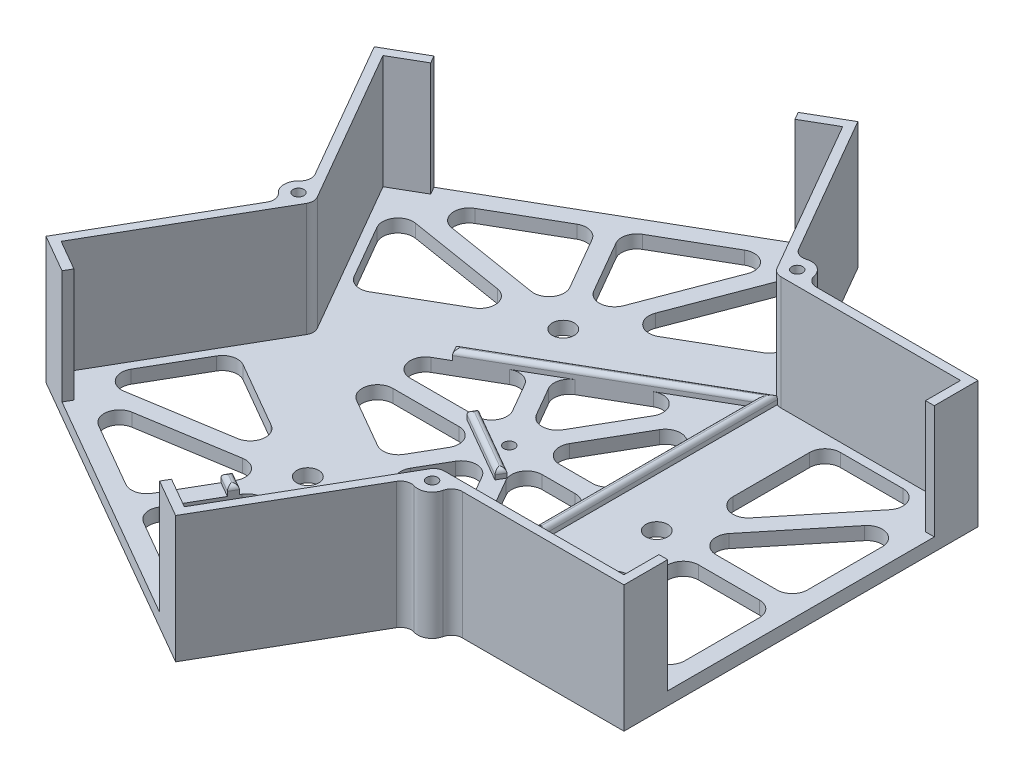
SolidWorks part; units mm, degrees
ref_plane "Front Plane" through (0, 0, 0) normal (0, 0, 1) x (1, 0, 0)
ref_plane "Top Plane" through (0, 0, 0) normal (0, 1, 0) x (1, 0, 0)
ref_plane "Right Plane" through (0, 0, 0) normal (1, 0, 0) x (0, 0, -1)
sketch "Sketch1" plane through (0, 0, 0) normal (0, 1, 0) x (1, 0, 0)
  line L0 (-19.4617, -68.9294) -> (-33.415, -32.2478)
  line L1 (-15.5479, 2.6989) -> (-16.7979, 0.5338)
  line L2 (50.5658, -38.8837) -> (50.5658, 42.1163)
  line L3 (-49.5423, -56.1811) -> (-14.4683, -76.4311)
  line L4 (-66.1729, -6.1649) -> (-66.1729, -0.3837)
  line L5 (-49.5423, -56.1811) -> (-84.6163, -35.9311)
  line L6 (-84.6163, -35.9311) -> (-68.1729, -7.4503)
  line L7 (-84.6163, 39.1637) -> (-68.1729, 10.683)
  line L8 (-14.4683, 79.6637) -> (1.9751, 51.183)
  line L9 (-66.1729, 1.6163) -> (-18.4823, 1.6163)
  line L10 (-84.6163, 39.1637) -> (-14.4683, 79.6637)
  line L11 (50.5658, 42.1163) -> (17.679, 42.1163)
  line L12 (50.5658, -38.8837) -> (17.679, -38.8837)
  line L13 (-14.4683, -76.4311) -> (1.9751, -47.9503)
  line L14 (2.0883, 48.8082) -> (7.095, 45.9176)
  line L15 (-33.7744, -24.8702) -> (-66.1729, -6.1649)
  line L16 (8.8271, 44.9176) -> (-15.0182, 3.6163)
  line L17 (-68.1729, -7.4503) -> (-68.1729, 10.683)
  line L18 (-38.91, -26.5239) -> (-65.6522, -11.0843)
  line L19 (19.5658, -4.0044) -> (19.5658, -34.8837)
  line L20 (1.9751, -47.9503) -> (17.679, -38.8837)
  line L21 (1.9751, 51.183) -> (17.679, 42.1163)
  line L22 (15.5658, -0.3837) -> (15.5658, -37.7943)
  line L23 (-29.1746, 35.3773) -> (-2.4324, 50.817)
  line L24 (10.5591, 43.9176) -> (15.5658, 41.027)
  line L25 (15.5658, -37.7943) -> (10.5591, -40.6849)
  line L26 (-30.3103, 30.1029) -> (2.0883, 48.8082)
  line L27 (8.8271, -41.6849) -> (-15.0182, -0.3837)
  line L28 (-17.3276, 3.6163) -> (-31.7524, 28.6007)
  line L29 (-17.4229, 1.6163) -> (-14.9229, 1.6163)
  line L30 (-17.3276, -0.3837) -> (-31.7524, -25.368)
  line L31 (-15.5479, 0.5338) -> (-16.7979, 2.6989)
  line L32 (-65.6522, 14.317) -> (-38.91, 29.7566)
  line L33 (19.5658, 38.1163) -> (19.5658, 7.2371)
  line L34 (-2.4324, -47.5843) -> (-29.1746, -32.1447)
  line L35 (-66.1729, 9.3975) -> (-33.7744, 28.1029)
  line L36 (15.5658, 41.027) -> (15.5658, 3.6163)
  line L37 (2.0883, -45.5755) -> (-30.3103, -26.8702)
  line L38 (7.095, 45.9176) -> (-16.1729, 5.6163)
  line L39 (-66.1729, -0.3837) -> (-19.637, -0.3837)
  line L40 (10.5591, -40.6849) -> (-12.7088, -0.3837)
  line L41 (10.5591, 43.9176) -> (-12.7088, 3.6163)
  line L42 (-66.1729, 3.6163) -> (-19.637, 3.6163)
  line L43 (7.095, -42.6849) -> (-16.1729, -2.3837)
  line L44 (-13.8635, 1.6163) -> (14.9859, 1.6163)
  line L45 (-16.1729, 5.6163) -> (-30.3103, 30.1029)
  line L46 (-12.7088, 3.6163) -> (15.5658, 3.6163)
  line L47 (-19.637, -0.3837) -> (-33.7744, -24.8702)
  line L48 (-19.637, 3.6163) -> (-33.7744, 28.1029)
  line L49 (-12.7088, -0.3837) -> (15.5658, -0.3837)
  line L50 (-16.1729, -2.3837) -> (-30.3103, -26.8702)
  line L51 (-53.8858, -0.3837) -> (-28.1992, -15.2138)
  line L52 (4.4155, -30.0439) -> (4.4155, -0.3837)
  line L53 (0.9514, 35.2766) -> (-24.7351, 20.4465)
  line L54 (4.4155, 3.6163) -> (4.4155, 33.2766)
  line L55 (-78.2327, 36.1069) -> (-65.6522, 14.317)
  line L56 (-75.6229, 39.7373) -> (-49.2744, 54.9496)
  line L57 (-15.0128, 72.6069) -> (-2.4324, 50.817)
  line L58 (-15.0128, -69.3743) -> (-2.4324, -47.5843)
  line L59 (-45.8103, -53.717) -> (-19.4617, -68.9294)
  line L60 (-49.2744, -51.717) -> (-75.6229, -36.5046)
  line L61 (-78.2327, -32.8743) -> (-65.6522, -11.0843)
  line L62 (44.7266, 38.1163) -> (19.5658, 38.1163)
  line L63 (-28.1992, 18.4465) -> (-53.8858, 3.6163)
  line L64 (46.5658, -30.8084) -> (46.5658, -0.3837)
  line L65 (44.7266, -34.8837) -> (19.5658, -34.8837)
  line L66 (-24.7351, -17.2138) -> (0.9514, -32.0439)
  line L67 (-38.91, -26.5239) -> (-78.2327, -32.8743)
  line L68 (-15.0128, -69.3743) -> (-29.1746, -32.1447)
  line L69 (-66.1729, 3.6163) -> (-66.1729, 9.3975)
  line L70 (44.7266, 38.1163) -> (19.5658, 7.2371)
  line L71 (7.095, -42.6849) -> (2.0883, -45.5755)
  line L72 (-29.1746, 35.3773) -> (-15.0128, 72.6069)
  line L73 (-78.2327, 36.1069) -> (-38.91, 29.7566)
  line L74 (-36.8791, -30.2478) -> (-75.6229, -36.5046)
  line L75 (46.5658, 34.041) -> (21.7753, 3.6163)
  line L76 (21.7753, -0.3837) -> (46.5658, -30.8084)
  line L77 (-33.415, 35.4804) -> (-19.4617, 72.162)
  line L78 (-75.6229, 39.7373) -> (-36.8791, 33.4804)
  line L79 (46.5658, 3.6163) -> (46.5658, 34.041)
  line L80 (19.5658, -4.0044) -> (44.7266, -34.8837)
  line L81 (-45.8103, 56.9496) -> (-19.4617, 72.162)
  line L82 (46.5658, 3.6163) -> (21.7753, 3.6163)
  line L83 (-33.415, 35.4804) -> (-45.8103, 56.9496)
  line L84 (-45.8103, -53.717) -> (-33.415, -32.2478)
  line L85 (46.5658, -0.3837) -> (21.7753, -0.3837)
  line L86 (-36.8791, 33.4804) -> (-49.2744, 54.9496)
  line L87 (-49.2744, -51.717) -> (-36.8791, -30.2478)
  circle A0 centre (-33.0423, -27.6023) radius 2.5
  circle A1 centre (-33.0423, 30.8349) radius 2.5
  circle A2 centre (17.5658, 1.6163) radius 2.5
  circle A3 centre (-16.1729, 1.6163) radius 1.25
  point P6 (50.5658, 1.6163)
  point P11 (-49.5423, -56.1811)
  point P14 (-49.5423, 59.4137)
  point P15 (-49.5423, -56.1811)
  point P26 (-68.1729, 1.6163)
  point P32 (9.8271, -43.417)
  point P36 (9.8271, 46.6496)
  point P64 (-16.1729, 1.6163)
  point P94 (-16.1729, 1.6163)
extrude "Boss-Extrude1" add sketch "Sketch1" along normal blind 3 contours L21 L8 L10 L7 L17 L6 L5 L3 L13 L20 L12 L2 L11 A3 A2 A1 A0 L87 L60 L74 L86 L78 | L69 L42 L63 L48 L35 | L53 L38 L14 L26 L45 | L54 L46 L36 L24 L41 | L52 L40 L25 L22 L49 | L71 L43 L66 L50 L37 | L51 L39 L4 L15 L47 region at (34.1224, 0, 36.8187) region at (-47.1024, 0, 10.9831) region at (-11.6196, 0, -34.7018) region at (10.2032, 0, 18.8697) region at (10.2032, 0, -22.1024) region at (-47.1024, 0, -14.2157) region at (-11.6196, 0, 31.4691)
sketch "Sketch2" plane through (0, 3, 0) normal (0, 1, 0) x (1, 0, 0)
  line L1 (-14.4683, 79.6637) -> (1.9751, 51.183)
  line L2 (1.9751, 51.183) -> (17.679, 42.1163)
  line L3 (17.679, 42.1163) -> (50.5658, 42.1163)
  line L5 (50.5658, -38.8837) -> (17.679, -38.8837)
  line L6 (17.679, -38.8837) -> (1.9751, -47.9503)
  line L7 (1.9751, -47.9503) -> (-14.4683, -76.4311)
  line L9 (-84.6163, -35.9311) -> (-68.1729, -7.4503)
  line L10 (-68.1729, -7.4503) -> (-68.1729, 10.683)
  line L11 (-68.1729, 10.683) -> (-84.6163, 39.1637)
  line L12 (-60.6289, 1.6163) -> (-62.9383, 1.6163)
  line L13 (6.055, 40.1163) -> (7.2097, 42.1163)
  line L14 (9.8271, -43.417) -> (7.316, -39.0678)
  line L15 (-60.6289, 1.6163) -> (-81.8843, 38.4317)
  line L17 (-15.2003, 76.9317) -> (6.055, 40.1163)
  line L18 (6.055, 40.1163) -> (48.5658, 40.1163)
  line L20 (48.5658, -36.8837) -> (6.055, -36.8837)
  line L21 (6.055, -36.8837) -> (-15.2003, -73.699)
  line L23 (-81.8843, -35.199) -> (-60.6289, 1.6163)
  line L24 (-15.2003, -73.699) -> (-81.8843, -35.199) construction
  line L25 (-14.4683, -76.4311) -> (-84.6163, -35.9311) construction
  line L26 (-81.8843, -35.199) -> (-74.9561, -39.199)
  line L27 (-74.9561, -39.199) -> (-75.9561, -40.9311)
  line L28 (-14.4683, -76.4311) -> (-84.6163, -35.9311) construction
  line L29 (-75.9561, -40.9311) -> (-84.6163, -35.9311)
  line L30 (-15.2003, -73.699) -> (-22.1285, -69.699)
  line L31 (-22.1285, -69.699) -> (-23.1285, -71.4311)
  line L32 (-23.1285, -71.4311) -> (-14.4683, -76.4311)
  line L33 (48.5658, 40.1163) -> (48.5658, 32.1163)
  line L34 (48.5658, 40.1163) -> (48.5658, -36.8837) construction
  line L35 (50.5658, 42.1163) -> (50.5658, -38.8837) construction
  line L36 (-84.6163, 39.1637) -> (-14.4683, 79.6637) construction
  line L37 (-81.8843, 38.4317) -> (-15.2003, 76.9317) construction
  line L38 (48.5658, 32.1163) -> (50.5658, 32.1163)
  line L39 (50.5658, -38.8837) -> (50.5658, 42.1163) construction
  line L40 (50.5658, 32.1163) -> (50.5658, 42.1163)
  line L41 (48.5658, -36.8837) -> (48.5658, -28.8837)
  line L42 (48.5658, -28.8837) -> (50.5658, -28.8837)
  line L43 (50.5658, -28.8837) -> (50.5658, -38.8837)
  line L44 (-15.2003, 76.9317) -> (-22.1285, 72.9317)
  line L45 (-22.1285, 72.9317) -> (-23.1285, 74.6637)
  line L46 (-84.6163, 39.1637) -> (-14.4683, 79.6637) construction
  line L47 (-23.1285, 74.6637) -> (-14.4683, 79.6637)
  line L48 (-81.8843, 38.4317) -> (-74.9561, 42.4317)
  line L49 (-74.9561, 42.4317) -> (-75.9561, 44.1637)
  line L50 (-75.9561, 44.1637) -> (-84.6163, 39.1637)
  line L51 (-84.6163, -35.9311) -> (-62.9383, 1.6163) construction
  line L52 (-63.1509, 1.6163) -> (-68.1729, 1.6163)
  line L53 (-62.9383, 1.6163) -> (-84.6163, 39.1637) construction
  line L54 (7.2097, -38.8837) -> (-14.4683, -76.4311) construction
  line L55 (7.2097, -38.8837) -> (6.055, -36.8837)
  line L56 (50.5658, -38.8837) -> (7.2097, -38.8837) construction
  line L57 (7.2097, 42.1163) -> (50.5658, 42.1163) construction
  line L58 (7.316, 42.3005) -> (9.8271, 46.6496)
  line L59 (-14.4683, 79.6637) -> (7.2097, 42.1163) construction
  circle A3 centre (-64.4009, 1.6163) radius 1.25
  circle A4 centre (7.941, -40.1503) radius 1.25
  circle A5 centre (7.941, 43.383) radius 1.25
  dimension "D1" = 2
extrude "Boss-Extrude2" add sketch "Sketch2" along normal blind 26 contours L49 L50 L11 L9 L29 L27 L26 L23 L15 L48 | A3 L10 L9 | A3 L11 L10 | L47 L45 L44 L17 L18 L33 L38 L40 L3 L1 | A5 L3 L2 | A5 L2 L1 | L43 L42 L41 L20 L21 L30 L31 L32 L7 L5 | A4 L7 L6 | A4 L6 L5 region at (-7.0061, 3, -64.9848) region at (34.1224, 3, 38.0067) region at (-75.629, 3, 22.1328)
sketch "Sketch3" plane through (0, 29, 0) normal (0, 1, 0) x (1, 0, 0)
  line L0 (-84.6163, 39.1637) -> (-64.8095, 4.8573)
  line L1 (-84.6163, -35.9311) -> (-64.8095, -1.6247)
  line L2 (-14.4683, -76.4311) -> (5.3385, -42.1247)
  line L3 (50.5658, -38.8837) -> (10.9521, -38.8837)
  line L4 (50.5658, 42.1163) -> (10.9521, 42.1163)
  line L6 (-14.4683, 79.6637) -> (5.3385, 45.3573)
  line L7 (1.9751, 51.183) -> (17.679, 42.1163)
  line L8 (-68.1729, -7.4503) -> (-68.1729, 10.683)
  line L9 (17.679, -38.8837) -> (1.9751, -47.9503)
  circle A0 centre (-64.4009, 1.6163) radius 3.2667
  circle A1 centre (7.941, 43.383) radius 3.2667
  circle A2 centre (7.941, -40.1503) radius 3.2667
  line M4 (-68.1729, 10.683) -> (-68.1729, -7.4503)
extrude "Cut-Extrude1" cut sketch "Sketch3" against normal through all contours A0 L0 L1 M4 | A2 L2 L9 L3 | A1 L4 L7 L6 region at (-66.6509, 29, -7.6779) region at (3.8139, 29, 45.1282) region at (14.3156, 29, -42.2977)
fillet "Fillet1" radius 2.5 9 edges at (6.055, 16, 36.8837) (-60.6289, 16, -1.6163) (6.055, 16, -40.1163) (5.3385, 14.5, -45.3573) (10.9521, 14.5, -42.1163) (5.3385, 14.5, 42.1247) (10.9521, 14.5, 38.8837) (-64.8095, 14.5, 1.6247) (-64.8095, 14.5, -4.8573)
fillet "Fillet2" radius 3.5 54 edges at (-33.415, 1.5, -35.4804) (-2.4324, 1.5, -50.817) (-19.4617, 1.5, -72.162) (-15.0128, 1.5, -72.6069) (-29.1746, 1.5, -35.3773) (-75.6229, 1.5, -39.7373) (-78.2327, 1.5, -36.1069) (-65.6522, 1.5, -14.317) (-38.91, 1.5, -29.7566) (-36.8791, 1.5, -33.4804) (-49.2744, 1.5, -54.9496) (-45.8103, 1.5, -56.9496) (46.5658, 1.5, -34.041) (44.7266, 1.5, -38.1163) (19.5658, 1.5, -38.1163) (46.5658, 1.5, 30.8084) (44.7266, 1.5, 34.8837) (19.5658, 1.5, 34.8837) (46.5658, 1.5, 0.3837) (46.5658, 1.5, -3.6163) (19.5658, 1.5, -7.2371) (21.7753, 1.5, -3.6163) (19.5658, 1.5, 4.0044) (21.7753, 1.5, 0.3837) (0.9514, 1.5, 32.0439) (4.4155, 1.5, 30.0439) (4.4155, 1.5, 0.3837) (4.4155, 1.5, -3.6163) (4.4155, 1.5, -33.2766) (0.9514, 1.5, -35.2766) (-24.7351, 1.5, -20.4465) (-12.7088, 1.5, 0.3837) (-16.1729, 1.5, 2.3837) (-16.1729, 1.5, -5.6163) (-12.7088, 1.5, -3.6163) (-28.1992, 1.5, -18.4465) (-19.637, 1.5, -3.6163) (-19.637, 1.5, 0.3837) (-28.1992, 1.5, 15.2138) (-24.7351, 1.5, 17.2138) (-53.8858, 1.5, -3.6163) (-53.8858, 1.5, 0.3837) (-2.4324, 1.5, 47.5843) (-19.4617, 1.5, 68.9294) (-15.0128, 1.5, 69.3743) (-29.1746, 1.5, 32.1447) (-33.415, 1.5, 32.2478) (-36.8791, 1.5, 30.2478) (-38.91, 1.5, 26.5239) (-45.8103, 1.5, 53.717) (-49.2744, 1.5, 51.717) (-65.6522, 1.5, 11.0843) (-75.6229, 1.5, 36.5046) (-78.2327, 1.5, 32.8743)
sketch "Sketch4" plane through (0, 3, 0) normal (0, 1, 0) x (1, 0, 0)
  line L0 (-57.3499, 1.6163) -> (-43.5001, 9.6125)
  line L1 (-61.3499, 1.6163) -> (-45.5001, 10.7672)
  line L2 (4.4155, -34.0439) -> (4.4155, -18.0516)
  line L3 (-57.3499, 1.6163) -> (4.4155, -34.0439)
  line L4 (6.4155, -37.508) -> (6.4155, -19.2063)
  line L5 (-61.3499, 1.6163) -> (6.4155, -37.508)
  line L6 (-65.3499, 1.6163) -> (8.4155, 44.2048)
  line L7 (8.4155, -40.9721) -> (8.4155, 44.2048)
  line L8 (-65.3499, 1.6163) -> (8.4155, -40.9721)
  line L9 (-81.8843, -35.199) -> (-51.8843, 16.7625) construction
  line L10 (-15.2003, -73.699) -> (14.7997, -21.7375) construction
  line L11 (-43.5001, 11.9219) -> (6.4155, -16.8969)
  line L12 (-47.5001, 11.9219) -> (-26.1384, -0.4113)
  line L13 (4.4155, -13.4328) -> (4.4155, 37.2766)
  line L14 (6.4155, -16.8969) -> (6.4155, 40.7407)
  line L15 (-51.8843, 16.7625) -> (14.7997, -21.7375) construction
  line L16 (-52.8843, 15.0304) -> (13.7997, -23.4696) construction
  line L17 (-39.5001, 11.9219) -> (4.4155, -13.4328)
  line L18 (-39.5001, 11.9219) -> (4.4155, 37.2766)
  line L19 (-57.3499, 1.6163) -> (4.4155, 37.2766) construction
  line L20 (-43.5001, 11.9219) -> (6.4155, 40.7407)
  line L21 (-61.3499, 1.6163) -> (6.4155, 40.7407) construction
  line L22 (4.4155, -34.0439) -> (4.4155, 37.2766) construction
  line L23 (-33.1145, 3.6163) -> (-25.1145, 3.6163)
  line L24 (6.4155, -37.508) -> (6.4155, 40.7407) construction
  line L25 (-125.5001, 11.9219) -> (47.4155, -87.911)
  line L28 (-125.5001, 11.9219) -> (47.4155, 111.7548) construction
  line L29 (47.4155, -87.911) -> (47.4155, 111.7548) construction
  line L30 (-22.4725, -2.5278) -> (-16.6121, -5.9113)
  line L31 (-5.9701, -12.0555) -> (-9.9701, -5.1273)
  line L32 (-12.9462, -8.0278) -> (8.4155, -20.361)
  line L33 (-9.9701, -5.1273) -> (-10.9701, -6.8593)
  line L34 (-25.1145, 3.6163) -> (-26.1145, 1.8843)
  line L35 (-39.5001, 11.9219) -> (-40.5001, 13.6539)
  line L36 (4.4155, -13.4328) -> (6.4155, -13.4328)
  line L37 (-126.5001, 10.1898) -> (46.4155, -89.6431)
  line L38 (-47.5244, -48.6859) -> (-40.5624, -36.6275)
  line L39 (-37.0983, -38.6275) -> (-44.0603, -50.6859)
  line L40 (-22.4725, -2.5278) -> (-21.4725, -0.7958)
  line L41 (-16.6121, -5.9113) -> (-15.6121, -4.1793)
  line L42 (4.4155, 37.2766) -> (7.941, 43.383) construction
  circle A0 centre (-63.5157, 1.6163) radius 2.5
  circle A1 centre (7.4984, 42.6163) radius 2.5
  circle A2 centre (7.4984, -39.3837) radius 2.5
  circle A3 centre (-25.6992, -3.8837) radius 3.5
  circle A4 centre (-16.1729, -9.3837) radius 3.5
  dimension "D1" = 2
  dimension "D3" = 2
  dimension "D2" = 2
  dimension "D4" = 41
  dimension "D5" = 2
extrude "Boss-Extrude3" add sketch "Sketch4" along normal blind 2 contours A1 L20 L35 L18 L13 L36 L14 | L39 L25 L38 L37 | L17 L34 L11 L33 region at (-18.0423, 3, 1.6215) region at (5.8908, 3, -39.8319) region at (-39.5423, 3, 38.8606)
fillet "Fillet3" radius 1 14 edges at (-17.2058, 5, -27.1029) (-17.5423, 5, -24.5992) (6.4155, 5, -13.4651) (4.4155, 5, -11.9219) (-17.5423, 5, 0.7555) (-18.5423, 5, 2.4875) (-39.0423, 5, 37.9946) (-40.0423, 5, 39.7266) (-41.2744, 5, 37.8606) (-37.8103, 5, 39.8606) (-10.4701, 5, 5.9933) (-25.6145, 5, -2.7503) (-40.0001, 5, -12.7879) (5.4155, 5, 13.4328)
